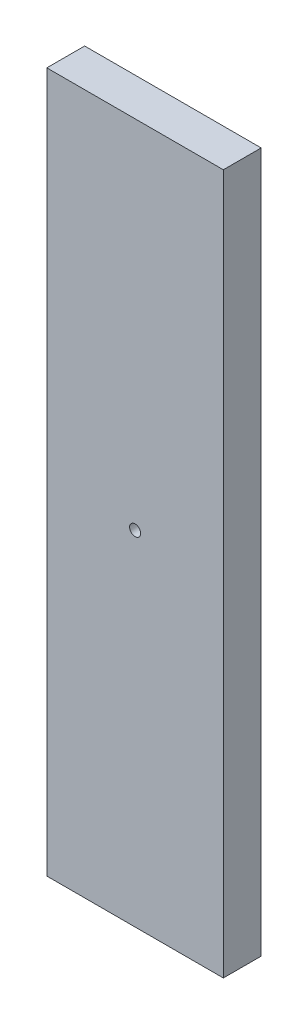
SolidWorks part; units mm, degrees
ref_plane "Front Plane" through (0, 0, 0) normal (0, 0, 1) x (1, 0, 0)
ref_plane "Top Plane" through (0, 0, 0) normal (0, 1, 0) x (1, 0, 0)
ref_plane "Right Plane" through (0, 0, 0) normal (1, 0, 0) x (0, 0, -1)
sketch "Sketch1" plane through (0, 0, 0) normal (0, 1, 0) x (1, 0, 0)
  line L1 (0, 0) -> (88.9, 0)
  line L2 (0, 0) -> (0, 19.05)
  line L3 (0, 19.05) -> (88.9, 19.05)
  line L4 (88.9, 0) -> (88.9, 19.05)
  dimension "D1" = 19.05
  dimension "D2" = 88.9
extrude "Boss-Extrude1" add sketch "Sketch1" along normal blind 352.522
sketch "Sketch2" plane through (0, 0, 0) normal (0, 0, 1) x (1, 0, 0)
  line L0 (44.45, 352.522) -> (44.45, 173.0637) construction
  line L1 (0, 352.522) -> (88.9, 352.522) construction
  line L2 (44.45, 0) -> (44.45, 173.0637) construction
  line L3 (0, 0) -> (88.9, 0) construction
  circle A0 centre (44.45, 173.0637) radius 2.7781
  dimension "D1" = 5.5562
  dimension "D3" = 173.0637
extrude "Cut-Extrude1" cut sketch "Sketch2" against normal through all contours A0 L0 L2 region at (44.45, 173.0637, 0)
